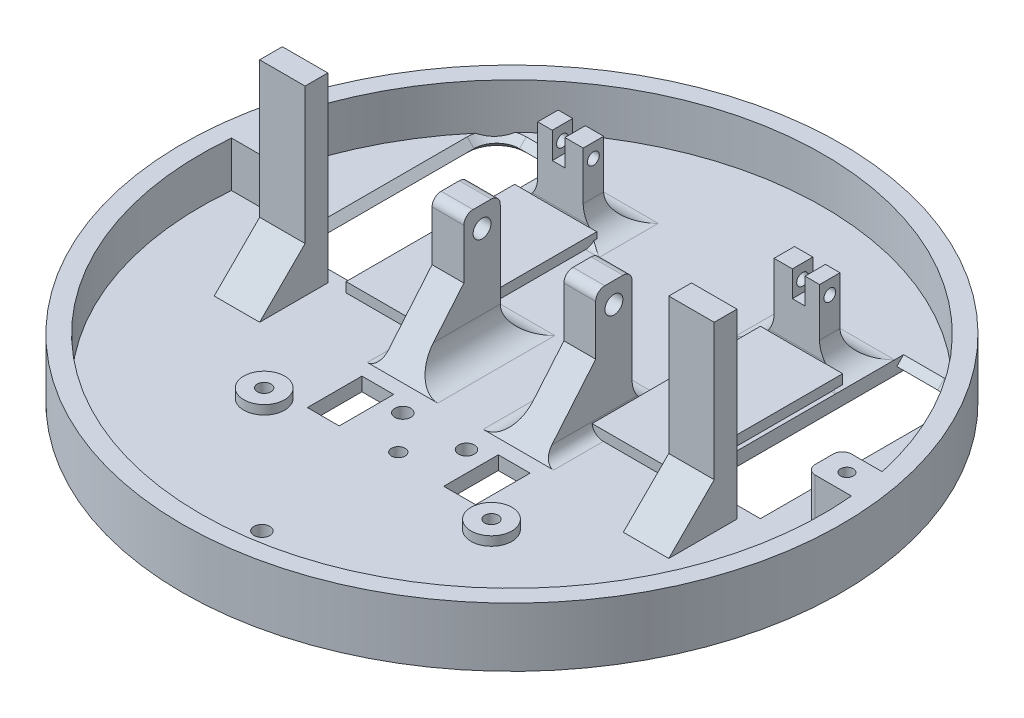
SolidWorks part; units mm, degrees
material "ABS"
ref_plane "Front Plane" through (0, 0, 0) normal (0, 0, 1) x (1, 0, 0)
ref_plane "Top Plane" through (0, 0, 0) normal (0, 1, 0) x (1, 0, 0)
ref_plane "Right Plane" through (0, 0, 0) normal (1, 0, 0) x (0, 0, -1)
sketch "Sketch2" plane through (0, 0, 0) normal (0, 1, 0) x (1, 0, 0)
  line L0 (0, 72.5) -> (0, -72.5) construction
  line L1 (-72.5, 0) -> (72.5, 0) construction
  circle A0 centre (0, 0) radius 72.5
  dimension "D1" = 145
extrude "Boss-Extrude1" add sketch "Sketch2" along normal blind 3
sketch "Sketch3" plane through (0, 3, 0) normal (0, 1, 0) x (1, 0, 0)
  line L0 (-72.5, 0) -> (72.5, 0) construction
  line L1 (-51, 47.6585) -> (-37, 47.6585)
  line L2 (-51, 47.6585) -> (-51, 2.1585)
  line L3 (-51, 2.1585) -> (-37, 2.1585)
  line L4 (-37, 47.6585) -> (-37, 2.1585)
  line L5 (0, 72.5) -> (0, -72.5) construction
  line L6 (37, 47.6585) -> (37, 2.1585)
  line L7 (51, 2.1585) -> (37, 2.1585)
  line L8 (51, 47.6585) -> (51, 2.1585)
  line L9 (51, 47.6585) -> (37, 47.6585)
  line L10 (-37, 47.6585) -> (-37, 20.3272) construction
  line L11 (0, 0) -> (0, 28.896) construction
  line L13 (0, 20.3272) -> (0, 72.5) construction
  circle A0 centre (0, 0) radius 72.5 construction
  circle A1 centre (0, 28.896) radius 6.68 construction
  point P17 (50, 0)
  dimension "D5" = 37
  dimension "D3" = 13.36
  dimension "D1" = 14
  dimension "D2" = 45.5
  dimension "D4" = 28.896
  dimension "D6" = 2.1585
extrude "Cut-Extrude1" cut sketch "Sketch3" against normal blind 5
fillet "Fillet1" radius 5 2 edges at (51, 1.5, -47.6585) (-51, 1.5, -47.6585)
sketch "Sketch4" plane through (0, 3, 0) normal (0, 1, 0) x (1, 0, 0)
  line L0 (0, 0) -> (0, 72.5) construction
  circle A0 centre (0, 0) radius 68.5
  circle A1 centre (0, 0) radius 72.5 construction
  circle A2 centre (0, 0) radius 72.5
  dimension "D1" = 4
extrude "Boss-Extrude2" add sketch "Sketch4" along normal blind 10
ref_plane "Plane1" through (0, 0, 72.5) normal (0, 0, 1) x (1, 0, 0)
sketch "草图5" plane through (0, 0, 0) normal (0, 1, 0) x (1, 0, 0)
  line L0 (21, 41.1715) -> (31, 41.1715)
  line L1 (0, 0) -> (0, 72.5) construction
  line L2 (31, 36.6715) -> (31, 41.1715)
  line L3 (21, 36.6715) -> (31, 36.6715)
  line L5 (21, 36.6715) -> (21, 41.1715)
  line L16 (0, 36.6715) -> (-21, 36.6715) construction
  line L18 (-21, 36.6715) -> (-31, 36.6715)
  line L19 (-21, 36.6715) -> (-21, 41.1715)
  line L20 (-21, 41.1715) -> (-31, 41.1715)
  line L21 (-31, 36.6715) -> (-31, 41.1715)
  circle A0 centre (0, 0) radius 72.5 construction
  dimension "D1" = 21
  dimension "D2" = 10
  dimension "D3" = 36.6715
  dimension "D4" = 4.5
extrude "凸台-拉伸2" add sketch "草图5" along normal blind 19.6
sketch "草图13" plane through (0, 0, 0) normal (0, 1, 0) x (1, 0, 0)
  line L0 (-37, 2.1585) -> (-37, -3.8875) construction
  line L1 (-37, 2.1585) -> (-23, 2.1585) construction
  line L2 (37, 2.1585) -> (18, 2.1585) construction
  line L3 (37, 2.1585) -> (37, -3.8875) construction
  line L4 (-37, -3.8875) -> (-23, -3.8875) construction
  line L5 (37, -3.8875) -> (18, -3.8875) construction
  line L6 (18, -3.8875) -> (18, 2.1585) construction
  line L7 (-23, 2.1585) -> (-23, -3.8875) construction
  line L8 (-37, 2.1585) -> (-37, 6.7325) construction
  line L9 (-9.305, 0.4303) -> (37, 0.4303) construction
  line L10 (18, 4.4303) -> (-18, 4.4303) construction
  line L11 (11, 8.4303) -> (18, 8.4303)
  line L12 (11, 8.4303) -> (11, 0.4303)
  line L13 (37, 47.6585) -> (37, 2.1585) construction
  line L14 (-11, 8.4303) -> (37, 8.4303) construction
  line L15 (0, 0) -> (0, 4.4303) construction
  line L17 (-37, 2.1585) -> (-37, 47.6585) construction
  line L18 (11, 0.4303) -> (18, 0.4303)
  line L19 (-18, 8.4303) -> (-11, 8.4303)
  line L20 (-18, 8.4303) -> (-18, 0.4303)
  line L21 (-18, 0.4303) -> (-11, 0.4303)
  line L22 (-11, 8.4303) -> (-11, 0.4303)
  line L23 (18, 8.4303) -> (18, 0.4303)
  point P28 (0, 0)
  dimension "D1" = 4.4303
  dimension "D2" = 8
  dimension "D3" = 11
  dimension "D4" = 7
extrude "凸台-拉伸4" add sketch "草图13" along normal blind 30
sketch "草图15" plane through (0, 0, 0) normal (1, 0, 0) x (0, 0, -1)
  line L0 (38.9215, 19.6) -> (38.9215, 16.48) construction
  line L1 (41.1715, 19.6) -> (36.6715, 19.6) construction
  circle A0 centre (38.9215, 16.48) radius 1.3
sketch "草图17" plane through (0, 0, 0) normal (1, 0, 0) x (0, 0, -1)
  line L0 (4.4303, 30) -> (4.4303, 25.39) construction
  line L1 (8.4303, 30) -> (0.4303, 30) construction
  circle A0 centre (4.4303, 25.39) radius 1.9685
extrude "切除-拉伸12" cut sketch "草图17" against normal blind 40 and the other way blind 40
extrude "切除-拉伸13" cut sketch "草图15" against normal blind 40 and the other way blind 40
sketch "Sketch5" plane through (0, 3, 0) normal (0, 1, 0) x (1, 0, 0)
  line L0 (0, 0) -> (0, -69.1541) construction
  line L1 (103.8296, 0) -> (-111.3937, 0) construction
  line L2 (-25, -29.5) -> (25, -29.5) construction
  circle A0 centre (0, 0) radius 68.5 construction
  circle A1 centre (-25, -29.5) radius 1.5
  circle A2 centre (25, -29.5) radius 1.5
  point P5 (0, 0)
  point P9 (0, -68.5)
  point P10 (0, -68.5)
  point P11 (0, -68.5)
  point P16 (0, -29.5)
  dimension "D1" = 3
  dimension "D2" = 25
  dimension "D3" = 39
extrude "Cut-Extrude2" cut sketch "Sketch5" against normal through all
sketch "Sketch7" plane through (0, 3, 0) normal (0, 1, 0) x (1, 0, 0)
  line L0 (0, 0) -> (0, 68.5) construction
  circle A0 centre (-25, -29.5) radius 4.5
  circle A1 centre (-25, -29.5) radius 1.5
  circle A2 centre (-25, -29.5) radius 1.5 construction
  circle A3 centre (0, 0) radius 68.5 construction
  circle A4 centre (25, -29.5) radius 1.5
  circle A5 centre (25, -29.5) radius 4.5
  dimension "D1" = 3
extrude "Boss-Extrude3" add sketch "Sketch7" along normal blind 2
sketch "Sketch8" plane through (0, 3, 0) normal (0, 1, 0) x (1, 0, 0)
  line L0 (0, 0) -> (0, -66.9892) construction
  circle A0 centre (0, -55) radius 5 construction
  circle A1 centre (0, -55) radius 1.75
  point P3 (0, -55)
  dimension "D1" = 10
  dimension "D3" = 3.5
  dimension "D2" = 55
extrude "Cut-Extrude4" cut sketch "Sketch8" against normal blind 10
sketch "Sketch9" plane through (0, 3, 0) normal (0, 1, 0) x (1, 0, 0)
  line L0 (0, 0) -> (0, -63.312) construction
  circle A0 centre (0, -25) radius 1.5
  dimension "D1" = 3
  dimension "D2" = 25
extrude "Cut-Extrude5" cut sketch "Sketch9" against normal blind 10
sketch "Sketch10" plane through (0, 0, 0) normal (0, -1, 0) x (1, 0, 0)
  line L0 (0, 55) -> (0, 0) construction
  line L1 (18.5, 26.5) -> (11.5, 26.5)
  line L2 (18.5, 26.5) -> (18.5, 14.5)
  line L3 (18.5, 14.5) -> (11.5, 14.5)
  line L4 (11.5, 26.5) -> (11.5, 14.5)
  line L5 (-11.5, 26.5) -> (-11.5, 14.5)
  line L6 (-18.5, 14.5) -> (-11.5, 14.5)
  line L7 (-18.5, 26.5) -> (-18.5, 14.5)
  line L8 (-18.5, 26.5) -> (-11.5, 26.5)
  line L9 (-15, 26.5) -> (-15, 14.5) construction
  line L10 (15, 26.5) -> (15, 14.5) construction
  dimension "D1" = 14.5
  dimension "D2" = 7
  dimension "D3" = 12
  dimension "D4" = 30
extrude "Cut-Extrude6" cut sketch "Sketch10" against normal blind 10
sketch "Sketch11" plane through (0, 3, 0) normal (0, 1, 0) x (1, 0, 0)
  line L0 (0, 0) -> (0, -25) construction
  circle A0 centre (7, -17) radius 1.75
  circle A1 centre (-7, -17) radius 1.75
  dimension "D1" = 3.5
extrude "Cut-Extrude7" cut sketch "Sketch11" against normal blind 10
sketch "Sketch12" plane through (0, 3, 0) normal (0, 1, 0) x (1, 0, 0)
  line L0 (66.9477, 14.5) -> (-66.9477, 14.5) construction
  line L1 (66.9477, 14.5) -> (58.1909, 14.5)
  line L2 (58.1909, 14.5) -> (58.1909, 6.5)
  line L3 (58.1909, 6.5) -> (68.1909, 6.5)
  line L4 (0, 0) -> (0, 14.5) construction
  line L5 (-58.1909, 6.5) -> (-68.1909, 6.5)
  line L6 (-58.1909, 14.5) -> (-58.1909, 6.5)
  line L7 (-66.9477, 14.5) -> (-58.1909, 14.5)
  line L8 (63.1909, 6.5) -> (63.1909, 14.5) construction
  circle A0 centre (0, 0) radius 68.5 construction
  arc A1 (68.1909, 6.5) -> (66.9477, 14.5) centre (0, 0) ccw
  arc A2 (-68.1909, 6.5) -> (-66.9477, 14.5) centre (0, 0) cw
  circle A3 centre (63.1909, 10.5) radius 1.4
  circle A4 centre (-63.1909, 10.5) radius 1.4
  dimension "D2" = 8
  dimension "D4" = 2.8
  dimension "D1" = 15
  dimension "D3" = 10
extrude "Boss-Extrude4" add sketch "Sketch12" along normal up to surface (10 mm away) up to face at (0, 13, 72.5)
extrude "Cut-Extrude8" cut sketch "Sketch12<2>" against normal blind 10 contours A3 | A4 region at (63.1909, 3, -10.5) region at (-63.1909, 3, -10.5)
sketch "Sketch12<2>" plane through (0, 3, 0) normal (0, 1, 0) x (1, 0, 0) same geometry as "Sketch12"
sketch "Sketch13" plane through (0, 0, -41.1715) normal (0, 0, -1) x (-1, 0, 0)
  line L0 (-27.8, 19.6) -> (-27.8, 13.92)
  line L1 (-31, 19.6) -> (-21, 19.6) construction
  line L2 (-27.8, 19.6) -> (-25.02, 19.6)
  line L3 (-25.02, 19.6) -> (-27.8, 19.6) construction
  line L4 (-25.02, 13.92) -> (-27.8, 13.92)
  line L5 (25.02, 19.6) -> (0, 19.6) construction
  line L6 (0, 36.5763) -> (0, -10.9159) construction
  line L7 (-21, 19.6) -> (-21, 3) construction
  line L8 (21, 19.6) -> (21, 3) construction
  line L9 (-25.02, 19.6) -> (0, 19.6) construction
  line L10 (-25.02, 13.92) -> (-25.02, 19.6)
  line L11 (31, 19.6) -> (27.8, 19.6) construction
  line L12 (21, 19.6) -> (31, 19.6) construction
  line L13 (27.8, 19.6) -> (27.8, 13.8192)
  line L14 (27.8, 13.8192) -> (25.02, 13.8192)
  line L15 (25.02, 13.8192) -> (25.02, 19.6)
  line L16 (25.02, 19.6) -> (27.8, 19.6)
  line L17 (-27.8, 19.6) -> (0, 19.6) construction
  dimension "D1" = 25.02
  dimension "D2" = 25.02
  dimension "D3" = 27.8
ref_plane "Plane2" through (21, 3, -41.1715) normal (1, 0, 0) x (0, 0, -1)
fillet "Fillet2" radius 6 10 edges at (-14.5, 3, -8.4303) (-11, 3, -4.4303) (11, 3, -4.4303) (14.5, 3, -8.4303) (-31, 3, -38.9215) (-26, 3, -41.1715) (-21, 3, -38.9215) (31, 3, -38.9215) (21, 3, -38.9215) (26, 3, -41.1715)
fillet "Fillet3" radius 2 4 edges at (-14.5, 30, -0.4303) (-14.5, 30, -8.4303) (14.5, 30, -0.4303) (14.5, 30, -8.4303)
fillet "Fillet4" radius 2 4 edges at (-58.1909, 8, -6.5) (-58.1909, 8, -14.5) (58.1909, 8, -6.5) (58.1909, 8, -14.5)
sketch "Sketch15" plane through (0, 3, 0) normal (0, 1, 0) x (1, 0, 0)
  line L0 (0, 48) -> (0, 0) construction
  line L1 (-20, 48) -> (20, 48)
  line L2 (-20, 48) -> (-20, 42)
  line L3 (-20, 42) -> (20, 42)
  line L4 (20, 48) -> (20, 42)
  line L5 (-20, 42) -> (-20, 40)
  line L6 (-20, 40) -> (-18.5, 40)
  line L7 (-18.5, 40) -> (-18.5, 42)
  line L8 (18.5, 40) -> (18.5, 42)
  line L9 (20, 40) -> (18.5, 40)
  line L10 (20, 42) -> (20, 40)
  point P4 (0, 0)
  point P5 (0, 48)
  dimension "D1" = 42
  dimension "D2" = 6
  dimension "D3" = 40
  dimension "D4" = 1.5
  dimension "D5" = 2
sketch "Sketch18" plane through (0, 3, 0) normal (0, 1, 0) x (1, 0, 0)
  line L0 (68.5, 0) -> (-68.5, 0) construction
  line L1 (0, 74.5) -> (0, 0) construction
  arc A0 (-68.1909, 6.5) -> (68.1909, 6.5) centre (0, 0) ccw construction
  point P5 (0, 0)
chamfer "倒角2" distance 1.5 angle 45 12 edges at (-51, 0, -22.4085) (-49.5355, 0, -46.1941) (-41.5, 0, -47.6585) (51, 3, -22.4085) (49.5355, 3, -46.1941) (41.5, 3, -47.6585) (-51, 3, -22.4085) (-49.5355, 3, -46.1941) (-41.5, 3, -47.6585) (51, 0, -22.4085) (49.5355, 0, -46.1941) (41.5, 0, -47.6585)
extrude "切除-拉伸14" cut sketch "Sketch13" against normal blind 6
chamfer "倒角3" distance 14 angle 40 2 edges at (11.5, 3, -0.4303) (-11.5, 3, -0.4303) first distance on face at (12.8485, 13.9515, -0.4303) first distance on face at (-12.8485, 13.9515, -0.4303)
fillet "圆角3" radius 2.5 4 edges at (-18, 3, -1.5566) (18, 3, -1.5566) (26, 3, -36.6715) (-26, 3, -36.6715)
sketch "草图19" plane through (0, 3, 0) normal (0, 1, 0) x (1, 0, 0)
  line L2 (36.0867, 36.6715) -> (36.0867, -0.3944) construction
  line L3 (36.0867, -0.3944) -> (18, -0.3944) construction
  line L4 (18, 0.4303) -> (18, -9.2193) construction
  line L6 (36.0867, -0.3944) -> (18, -0.3944)
  line L7 (36.0867, -0.3944) -> (36.0867, 36.6715)
  line L8 (36.0867, 36.6715) -> (18, 36.6715)
  line L9 (18, -0.3944) -> (18, 36.6715)
  line L10 (19.8734, 36.6715) -> (32.1266, 36.6715) construction
  line L11 (0, -0.3944) -> (0, 35.576) construction
  line L12 (-36.0867, -0.3944) -> (-18, -0.3944) construction
  line L13 (-36.0867, 36.6715) -> (-36.0867, -0.3944) construction
  line L14 (-18, -0.3944) -> (-18, 36.6715)
  line L15 (-36.0867, 36.6715) -> (-18, 36.6715)
  line L16 (-36.0867, -0.3944) -> (-36.0867, 36.6715)
  line L17 (-36.0867, -0.3944) -> (-18, -0.3944)
  circle A1 centre (0, 28.896) radius 6.68 construction
  point P8 (36.0867, 36.6715)
  dimension "D1" = 37.0659
  dimension "D2" = 18.0867
extrude "凸台-拉伸6" add sketch "草图19" along normal blind 2.16
extrude "凸台-拉伸8" [suppressed] add sketch "Sketch15" along normal blind 45 contours L0 L1 L2 L3 | L1 L0 L3 L4 | L6 L7 L3 L5 | L10 L3 L8 L9
ref_plane "基准面1" [suppressed] through (0, 0, -42) normal (0, 0, 1) x (1, 0, 0)
sketch "草图20" [suppressed] plane through (0, 0, -42) normal (0, 0, 1) x (1, 0, 0)
  line L0 (0, 0) -> (0, 62.4108) construction
  line L1 (0, 3) -> (-7.5, 3) construction
  line L2 (-15, 3) -> (15, 3) construction
  line L3 (-7.5, 3) -> (-7.5, 57.2613)
  line L4 (-7.5, 57.2613) -> (7.5, 57.2613)
  line L5 (7.5, 3) -> (7.5, 57.2613)
  line L11 (-7.5, 3) -> (7.5, 3)
  point P13 (0, 3)
extrude "切除-拉伸15" [suppressed] cut sketch "草图20" against normal blind 20
fillet "圆角6" [suppressed] radius 5
sketch "草图21" [suppressed] plane through (0, 0, -42) normal (0, 0, 1) x (1, 0, 0)
  line L0 (0, 0.167) -> (0, 79.2312) construction
  line L1 (0, 0) -> (0, 39) construction
  line L2 (0, 39) -> (11.5, 39) construction
  circle A0 centre (11.5, 39) radius 2
  circle A1 centre (-11.5, 39) radius 2
  point P7 (0, 39)
  point P8 (11.5, 39)
  dimension "D1" = 90
  dimension "D2" = 11.5
extrude "切除-拉伸16" [suppressed] cut sketch "草图21" against normal blind 20
fillet "圆角7" [suppressed] radius 3
sketch "Sketch20" plane through (0, 3, 0) normal (0, 1, 0) x (1, 0, 0)
  line L0 (0, -72.5) -> (0, 72.5) construction
  line L1 (-50, -5.5) -> (-40, -0.5) construction
  line L2 (50, -0.5) -> (40, -0.5)
  line L3 (50, -0.5) -> (50, -5.5)
  line L4 (50, -5.5) -> (40, -5.5)
  line L5 (40, -0.5) -> (40, -5.5)
  line L6 (50, -0.5) -> (40, -5.5) construction
  line L7 (50, -5.5) -> (40, -0.5) construction
  line L8 (-50, -0.5) -> (-40, -5.5) construction
  line L9 (-40, -0.5) -> (-40, -5.5)
  line L10 (-50, -5.5) -> (-40, -5.5)
  line L11 (-50, -0.5) -> (-50, -5.5)
  line L12 (-50, -0.5) -> (-40, -0.5)
  circle A0 centre (0, 0) radius 72.5 construction
  point P5 (45, -3)
  point P14 (-45, -3)
  point P15 (0, 0)
  dimension "D1" = 45
  dimension "D2" = 10
  dimension "D3" = 3
  dimension "D4" = 5
extrude "Boss-Extrude5" add sketch "Sketch20" along normal blind 40
chamfer "Chamfer1" distance 10 angle 45 2 edges at (-45, 3, 5.5) (45, 3, 5.5)
